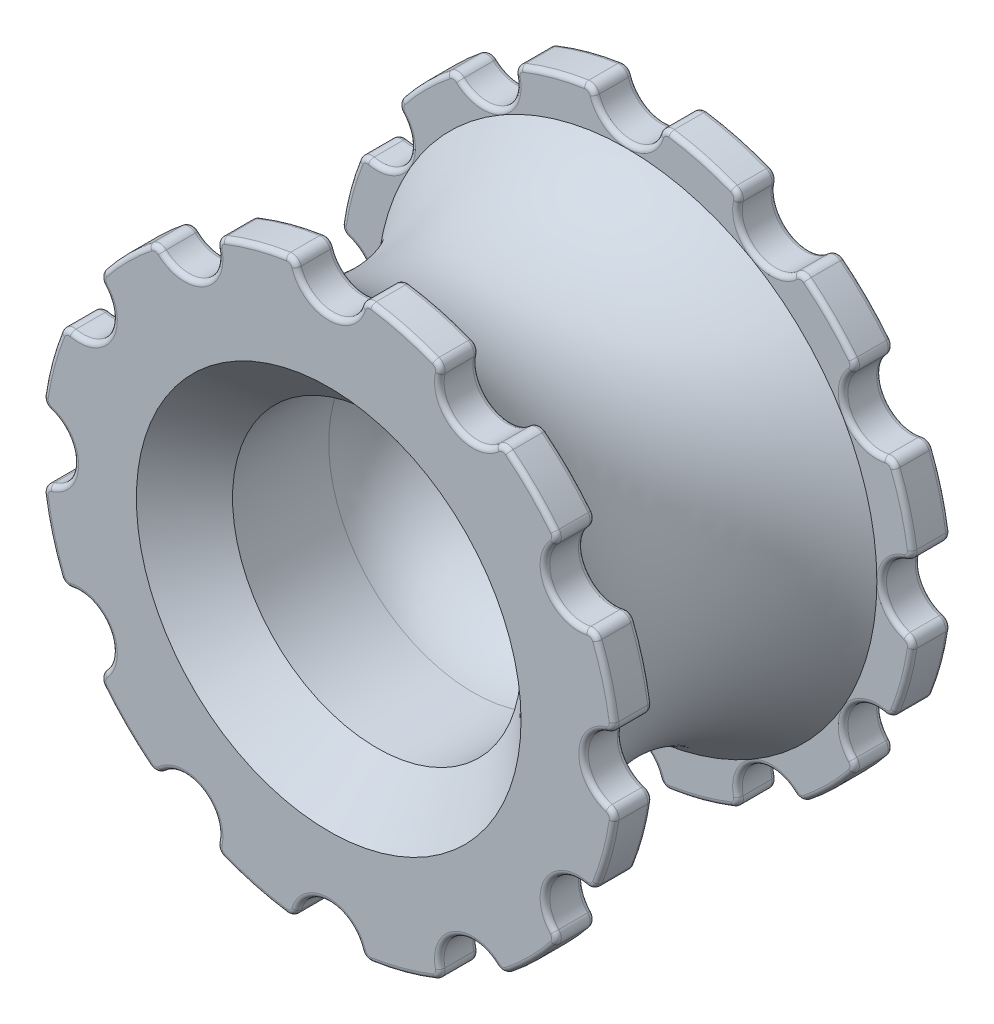
SolidWorks part; units mm, degrees
ref_plane "Спереди" through (0, 0, 0) normal (0, 0, 1) x (1, 0, 0)
ref_plane "Сверху" through (0, 0, 0) normal (0, 1, 0) x (1, 0, 0)
ref_plane "Справа" through (0, 0, 0) normal (1, 0, 0) x (0, 0, -1)
sketch "Эскиз1" plane through (0, 0, 0) normal (0, 0, 1) x (1, 0, 0)
  line L0 (0, -796.897) -> (0, 39047.9522) construction
  circle A0 centre (0, 0) radius 30 construction
  arc A1 (-3.494, 29.7958) -> (3.494, 29.7958) centre (0, 30) ccw
  arc A2 (3.494, 29.7958) -> (11.872, 27.551) centre (0, 0) cw
  arc A3 (11.872, 27.551) -> (17.9238, 24.0569) centre (15, 25.9808) ccw
  arc A4 (17.9238, 24.0569) -> (24.0569, 17.9238) centre (0, 0) cw
  arc A5 (24.0569, 17.9238) -> (27.551, 11.872) centre (25.9808, 15) ccw
  arc A6 (27.551, 11.872) -> (29.7958, 3.494) centre (0, 0) cw
  arc A7 (29.7958, 3.494) -> (29.7958, -3.494) centre (30, 0) ccw
  arc A8 (29.7958, -3.494) -> (27.551, -11.872) centre (0, 0) cw
  arc A9 (27.551, -11.872) -> (24.0569, -17.9238) centre (25.9808, -15) ccw
  arc A10 (24.0569, -17.9238) -> (17.9238, -24.0569) centre (0, 0) cw
  arc A11 (17.9238, -24.0569) -> (11.872, -27.551) centre (15, -25.9808) ccw
  arc A12 (11.872, -27.551) -> (3.494, -29.7958) centre (0, 0) cw
  arc A13 (3.494, -29.7958) -> (-3.494, -29.7958) centre (0, -30) ccw
  arc A14 (-3.494, -29.7958) -> (-11.872, -27.551) centre (0, 0) cw
  arc A15 (-11.872, -27.551) -> (-17.9238, -24.0569) centre (-15, -25.9808) ccw
  arc A16 (-17.9238, -24.0569) -> (-24.0569, -17.9238) centre (0, 0) cw
  arc A17 (-24.0569, -17.9238) -> (-27.551, -11.872) centre (-25.9808, -15) ccw
  arc A18 (-27.551, -11.872) -> (-29.7958, -3.494) centre (0, 0) cw
  arc A19 (-29.7958, -3.494) -> (-29.7958, 3.494) centre (-30, 0) ccw
  arc A20 (-29.7958, 3.494) -> (-27.551, 11.872) centre (0, 0) cw
  arc A21 (-27.551, 11.872) -> (-24.0569, 17.9238) centre (-25.9808, 15) ccw
  arc A22 (-24.0569, 17.9238) -> (-17.9238, 24.0569) centre (0, 0) cw
  arc A23 (-17.9238, 24.0569) -> (-11.872, 27.551) centre (-15, 25.9808) ccw
  arc A24 (-11.872, 27.551) -> (-3.494, 29.7958) centre (0, 0) cw
  point P12 (0, 0)
  point P13 (0, 0)
  point P55 (0, 0)
  dimension "D1" = 3.5
  dimension "D2" = 0
  dimension "D3" = 30
  dimension "D4" = 12
  dimension "D5" = 60
extrude "Бобышка-Вытянуть1" add sketch "Эскиз1" along normal blind 35
fillet "Скругление1" radius 1 24 edges at (3.494, 29.7958, 17.5) (11.872, 27.551, 17.5) (17.9238, 24.0569, 17.5) (29.7958, 3.494, 17.5) (27.551, 11.872, 17.5) (24.0569, 17.9238, 17.5) (29.7958, -3.494, 17.5) (27.551, -11.872, 17.5) (17.9238, -24.0569, 17.5) (24.0569, -17.9238, 17.5) (11.872, -27.551, 17.5) (-11.872, -27.551, 17.5) (3.494, -29.7958, 17.5) (-3.494, -29.7958, 17.5) (-17.9238, -24.0569, 17.5) (-24.0569, -17.9238, 17.5) (-27.551, -11.872, 17.5) (-29.7958, -3.494, 17.5) (-29.7958, 3.494, 17.5) (-27.551, 11.872, 17.5) (-24.0569, 17.9238, 17.5) (-17.9238, 24.0569, 17.5) (-11.872, 27.551, 17.5) (-3.494, 29.7958, 17.5)
sketch "Эскиз2" plane through (0, 0, 0) normal (0, 1, 0) x (1, 0, 0)
  line L0 (0, -1000) -> (0, 49000) construction
  line L2 (-30, -4) -> (-30, -31)
  line L5 (-30, -4) -> (-26, -4)
  line L6 (-30, -31) -> (-26, -31)
  arc A1 (-26, -4) -> (-26, -31) centre (-40.7564, -17.5) cw
  dimension "D3" = 4
  dimension "D5" = 20
  dimension "D1" = 4
  dimension "D2" = 27
  dimension "D4" = 30
revolve "Вырез-Повернуть1" cut sketch "Эскиз2" angle 360 about L0
sketch "Эскиз3" plane through (0, 0, 35) normal (0, 0, 1) x (1, 0, 0)
  circle A0 centre (0, 0) radius 15
  dimension "D1" = 30
extrude "Вырез-Вытянуть1" cut sketch "Эскиз3" against normal blind 25
fillet "Скругление2" radius 0.5 192 edges at (-29.5254, -3.7689, 4) (-26.5, 0, 4) (-29.5254, 3.7689, 4) (-28.9778, 7.7646, 4) (-27.4542, 11.4987, 4) (-22.9497, 13.25, 4) (-23.6853, 18.0266, 4) (-21.2132, 21.2132, 4) (-18.0266, 23.6853, 4) (-13.25, 22.9497, 4) (-11.4987, 27.4542, 4) (-7.7646, 28.9778, 4) (-3.7689, 29.5254, 4) (0, 26.5, 4) (3.7689, 29.5254, 4) (7.7646, 28.9778, 4) (11.4987, 27.4542, 4) (13.25, 22.9497, 4) (18.0266, 23.6853, 4) (21.2132, 21.2132, 4) (23.6853, 18.0266, 4) (22.9497, 13.25, 4) (27.4542, 11.4987, 4) (28.9778, 7.7646, 4) (29.5254, 3.7689, 4) (26.5, 0, 4) (29.5254, -3.7689, 4) (28.9778, -7.7646, 4) (27.4542, -11.4987, 4) (22.9497, -13.25, 4) (23.6853, -18.0266, 4) (21.2132, -21.2132, 4) (18.0266, -23.6853, 4) (13.25, -22.9497, 4) (11.4987, -27.4542, 4) (7.7646, -28.9778, 4) (3.7689, -29.5254, 4) (0, -26.5, 4) (-3.7689, -29.5254, 4) (-7.7646, -28.9778, 4) (-11.4987, -27.4542, 4) (-13.25, -22.9497, 4) (-18.0266, -23.6853, 4) (-21.2132, -21.2132, 4) (-23.6853, -18.0266, 4) (-22.9497, -13.25, 4) (-27.4542, -11.4987, 4) (-29.5254, -3.7689, 31) (-26.5, 0, 31) (-29.5254, 3.7689, 31) (-28.9778, 7.7646, 31) (-27.4542, 11.4987, 31) (-22.9497, 13.25, 31) (-23.6853, 18.0266, 31) (-21.2132, 21.2132, 31) (-18.0266, 23.6853, 31) (-13.25, 22.9497, 31) (-11.4987, 27.4542, 31) (-7.7646, 28.9778, 31) (-3.7689, 29.5254, 31) (0, 26.5, 31) (3.7689, 29.5254, 31) (7.7646, 28.9778, 31) (11.4987, 27.4542, 31) (13.25, 22.9497, 31) (18.0266, 23.6853, 31) (21.2132, 21.2132, 31) (23.6853, 18.0266, 31) (22.9497, 13.25, 31) (27.4542, 11.4987, 31) (28.9778, 7.7646, 31) (29.5254, 3.7689, 31) (26.5, 0, 31) (29.5254, -3.7689, 31) (28.9778, -7.7646, 31) (27.4542, -11.4987, 31) (22.9497, -13.25, 31) (23.6853, -18.0266, 31) (21.2132, -21.2132, 31) (18.0266, -23.6853, 31) (13.25, -22.9497, 31) (11.4987, -27.4542, 31) (7.7646, -28.9778, 31) (3.7689, -29.5254, 31) (0, -26.5, 31) (-3.7689, -29.5254, 31) (-7.7646, -28.9778, 31) (-11.4987, -27.4542, 31) (-13.25, -22.9497, 31) (-18.0266, -23.6853, 31) (-21.2132, -21.2132, 31) (-23.6853, -18.0266, 31) (-22.9497, -13.25, 31) (-27.4542, -11.4987, 31) (-29.5254, 3.7689, 35) (-28.9778, 7.7646, 35) (-27.4542, 11.4987, 35) (-22.9497, 13.25, 35) (-23.6853, 18.0266, 35) (-21.2132, 21.2132, 35) (-18.0266, 23.6853, 35) (-13.25, 22.9497, 35) (-11.4987, 27.4542, 35) (-7.7646, 28.9778, 35) (-3.7689, 29.5254, 35) (0, 26.5, 35) (3.7689, 29.5254, 35) (7.7646, 28.9778, 35) (11.4987, 27.4542, 35) (13.25, 22.9497, 35) (18.0266, 23.6853, 35) (21.2132, 21.2132, 35) (23.6853, 18.0266, 35) (22.9497, 13.25, 35) (27.4542, 11.4987, 35) (28.9778, 7.7646, 35) (29.5254, 3.7689, 35) (26.5, 0, 35) (29.5254, -3.7689, 35) (28.9778, -7.7646, 35) (27.4542, -11.4987, 35) (22.9497, -13.25, 35) (23.6853, -18.0266, 35) (21.2132, -21.2132, 35) (18.0266, -23.6853, 35) (13.25, -22.9497, 35) (11.4987, -27.4542, 35) (7.7646, -28.9778, 35) (3.7689, -29.5254, 35) (0, -26.5, 35) (-3.7689, -29.5254, 35) (-7.7646, -28.9778, 35) (-11.4987, -27.4542, 35) (-13.25, -22.9497, 35) (-18.0266, -23.6853, 35) (-21.2132, -21.2132, 35) (-23.6853, -18.0266, 35) (-22.9497, -13.25, 35) (-27.4542, -11.4987, 35) (-28.9778, -7.7646, 35) (-29.5254, -3.7689, 35) (3.7689, 29.5254, 0) (0, 26.5, 0) (-3.7689, 29.5254, 0) (-7.7646, 28.9778, 0) (-11.4987, 27.4542, 0) (-13.25, 22.9497, 0) (-18.0266, 23.6853, 0) (-21.2132, 21.2132, 0) (-23.6853, 18.0266, 0) (-22.9497, 13.25, 0) (-27.4542, 11.4987, 0) (-28.9778, 7.7646, 0) (-29.5254, 3.7689, 0) (-26.5, 0, 0) (-29.5254, -3.7689, 0) (-28.9778, -7.7646, 0) (-27.4542, -11.4987, 0) (-22.9497, -13.25, 0) (-23.6853, -18.0266, 0) (-21.2132, -21.2132, 0) (-18.0266, -23.6853, 0) (-13.25, -22.9497, 0) (-11.4987, -27.4542, 0) (-7.7646, -28.9778, 0) (-3.7689, -29.5254, 0) (0, -26.5, 0) (3.7689, -29.5254, 0) (7.7646, -28.9778, 0) (11.4987, -27.4542, 0) (13.25, -22.9497, 0) (18.0266, -23.6853, 0) (21.2132, -21.2132, 0) (23.6853, -18.0266, 0) (22.9497, -13.25, 0) (27.4542, -11.4987, 0) (28.9778, -7.7646, 0) (29.5254, -3.7689, 0) (26.5, 0, 0) (29.5254, 3.7689, 0) (28.9778, 7.7646, 0) (27.4542, 11.4987, 0) (22.9497, 13.25, 0) (23.6853, 18.0266, 0) (21.2132, 21.2132, 0) (18.0266, 23.6853, 0) (13.25, 22.9497, 0) (11.4987, 27.4542, 0) (7.7646, 28.9778, 0) (-28.9778, -7.7646, 4) (-28.9778, -7.7646, 31) (-26.5, 0, 35)
fillet "Скругление3" radius 10 1 edges at (15, 0, 10)
chamfer "Фаска1" distance 5 angle 45 1 edges at (15, 0, 35)
sketch "Эскиз4" plane through (0, 0, 0) normal (0, 0, -1) x (-1, 0, 0)
  circle A0 centre (0, 0) radius 6
  dimension "D1" = 12
extrude "Бобышка-Вытянуть2" add sketch "Эскиз4" along normal blind 1
sketch "Эскиз5" plane through (0, 0, -1) normal (0, 0, -1) x (-1, 0, 0)
  circle A0 centre (0, 0) radius 3.75
  dimension "D1" = 7.5
extrude "Бобышка-Вытянуть3" add sketch "Эскиз5" along normal blind 3.5
sketch "Эскиз6" plane through (0, 0, -4.5) normal (0, 0, -1) x (-1, 0, 0)
  circle A0 centre (0, 0) radius 2.7
  dimension "D1" = 5.4
extrude "Вырез-Вытянуть2" cut sketch "Эскиз6" against normal blind 1
sketch "Эскиз7" plane through (0, 0, -3.5) normal (0, 0, -1) x (-1, 0, 0)
  line L0 (-1.85, 1.9666) -> (-1.85, -1.9666)
  line L2 (1.85, 1.9666) -> (1.85, -1.9666)
  arc A0 (-1.85, -1.9666) -> (1.85, -1.9666) centre (0, 0) ccw
  circle A1 centre (0, 0) radius 2.7 construction
  arc A2 (1.85, 1.9666) -> (-1.85, 1.9666) centre (0, 0) ccw
  dimension "D1" = 3.7
extrude "Вырез-Вытянуть3" cut sketch "Эскиз7" against normal blind 8
sketch "Эскиз8" plane through (0, 0, 10) normal (0, 0, 1) x (1, 0, 0)
  circle A0 centre (0, 0) radius 1.475
  dimension "D1" = 2.95
extrude "Вырез-Вытянуть4" cut sketch "Эскиз8" against normal blind 17
